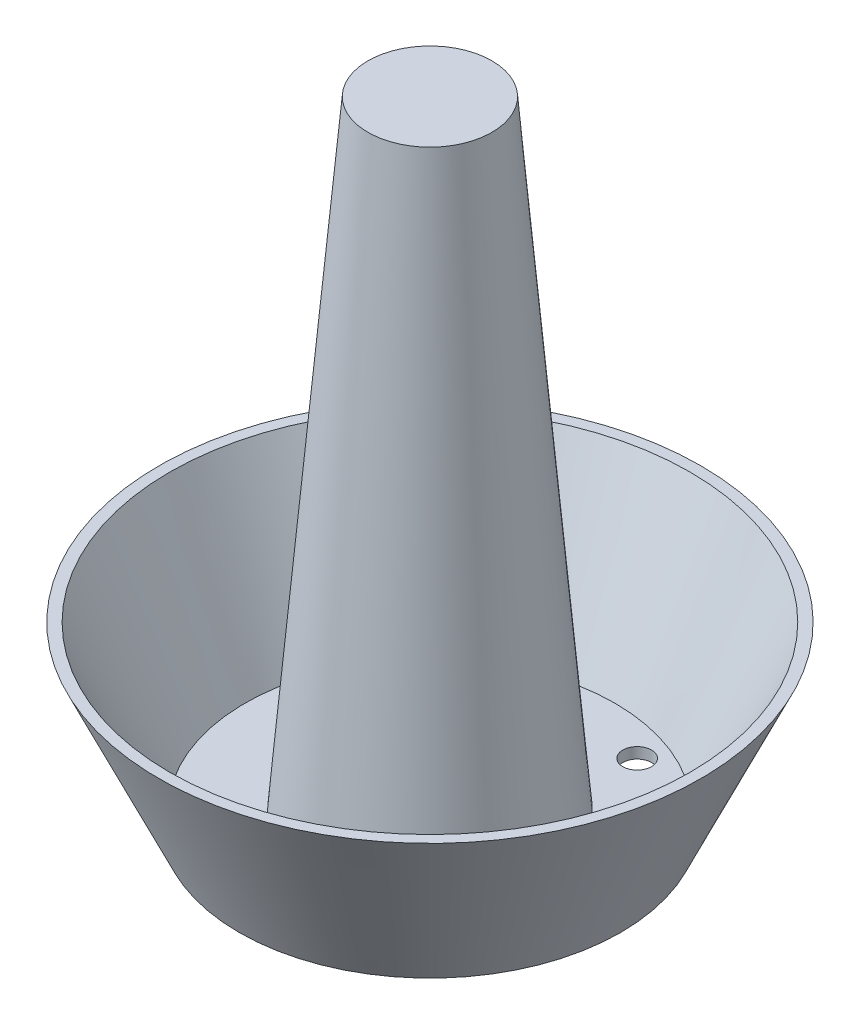
SolidWorks part; units mm, degrees
ref_plane "Front" through (0, 0, 0) normal (0, 0, 1) x (1, 0, 0)
ref_plane "Top" through (0, 0, 0) normal (0, 1, 0) x (1, 0, 0)
ref_plane "Right" through (0, 0, 0) normal (1, 0, 0) x (0, 0, -1)
sketch "Sketch1" plane through (0, 0, 0) normal (0, 0, 1) x (1, 0, 0)
  line L0 (0, 184.15) -> (18.161, 184.15)
  line L1 (0, -50) -> (0, 50) construction
  line L2 (18.161, 184.15) -> (33.655, 3.175)
  line L3 (33.655, 3.175) -> (54.1734, 3.175)
  line L4 (54.1734, 3.175) -> (76.2, 50.8)
  line L5 (76.2, 50.8) -> (79.375, 50.8)
  line L6 (79.375, 50.8) -> (55.88, 0)
  line L7 (50, 0) -> (-50, 0) construction
  line L8 (55.88, 0) -> (0, 0)
  line L9 (0, 0) -> (0, 184.15)
  dimension "D1" = 184.15
  dimension "D2" = 3.175
  dimension "D3" = 50.8
  dimension "D4" = 55.88
  dimension "D5" = 3.175
  dimension "D6" = 18.161
  dimension "D7" = 79.375
  dimension "D8" = 33.655
revolve "Revolve1" add sketch "Sketch1" angle 360 about L9
sketch "Sketch4" plane through (0, 0, 0) normal (0, -1, 0) x (1, 0, 0)
  line L0 (0, 0) -> (0, 43.434) construction
  line L1 (0, 43.434) -> (17.272, 43.434) construction
  line L2 (0, 43.434) -> (-17.272, 43.434) construction
  dimension "D1" = 34.544
  dimension "D2" = 43.434
hole_wizard "5/16 Clearance Hole1" positions "Sketch6" profile "Sketch5" hole size "5/16" standard "ANSI Inch" end condition through all
sketch "Sketch6" plane through (0, 0, 0) normal (0, -1, 0) x (-1, 0, 0)
  point P0 (17.272, -43.434)
  point P3 (-17.272, -43.434)
sketch "Sketch5" plane through (-17.272, 0, 43.434) normal (1, 0, 0) x (0, 0, -1)
  line L0 (0, 0) -> (0, 184.15)
  line L1 (0, 184.15) -> (4.2164, 184.15)
  line L2 (4.2164, 184.15) -> (4.2164, 0)
  line L5 (4.2164, 0) -> (0, 0)
  line L11 (0, -6.35) -> (0, 107.95) construction
  dimension "Thru Hole Dia." = 8.4328
  dimension "Thru Hole Depth" = 184.15
sketch "Sketch2" plane through (0, 0, 0) normal (0, -1, 0) x (1, 0, 0)
  line L0 (0, 0) -> (-14.986, 0) construction
  circle A0 centre (-14.986, 0) radius 5.461
  dimension "D1" = 10.922
  dimension "D2" = 14.986
extrude "RF Connector" add sketch "Sketch2" along normal blind 12.7
mirror "Mirror1" about plane through (0, 0, 0) normal (0, 0, 1) of "5/16 Clearance Hole1"
